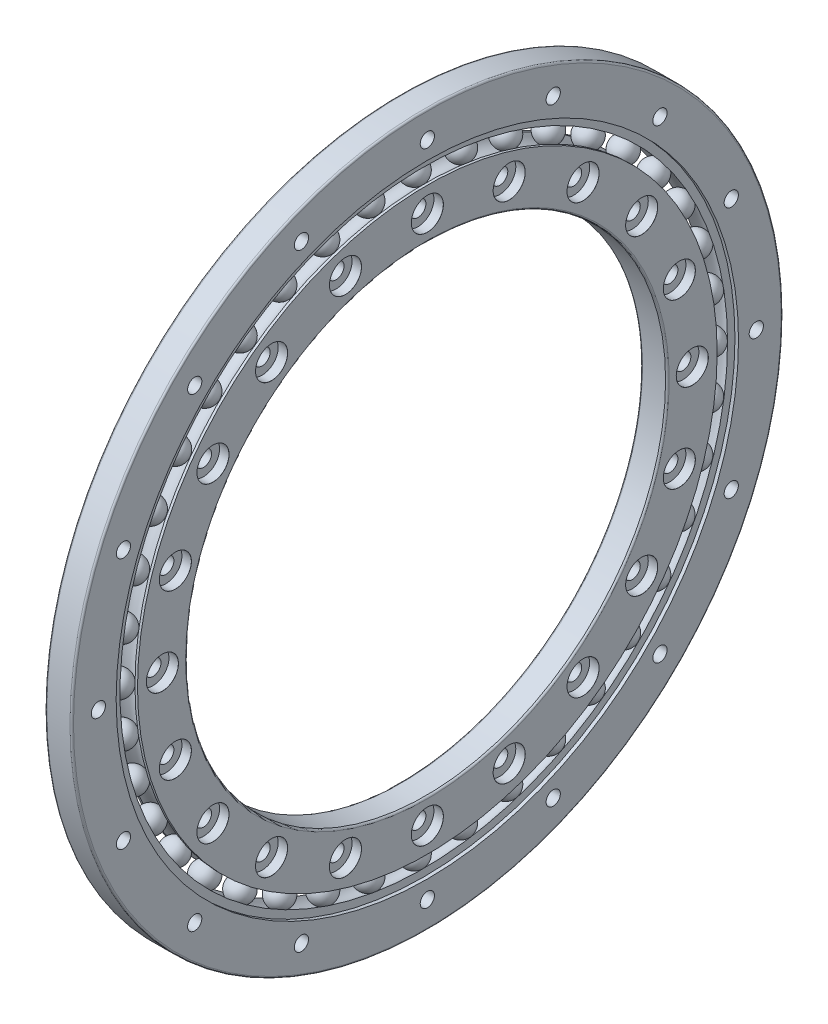
SolidWorks part; units mm, degrees
ref_plane "Front Plane" through (0, 0, 0) normal (0, 0, 1) x (1, 0, 0)
ref_plane "Top Plane" through (0, 0, 0) normal (0, 1, 0) x (1, 0, 0)
ref_plane "Right Plane" through (0, 0, 0) normal (1, 0, 0) x (0, 0, -1)
sketch "Sketch1" plane through (0, 0, 0) normal (0, 0, 1) x (1, 0, 0)
  line L0 (0, 0) -> (0, 185) construction
  line L1 (-4.3728, 170) -> (-4.3728, 163) construction
  line L2 (7.5, 170) -> (-7.5, 170)
  line L3 (7.5, 170) -> (7.5, 200)
  line L4 (7.5, 200) -> (-7.5, 200)
  line L5 (-7.5, 170) -> (-7.5, 200)
  line L6 (7.5, 170) -> (-7.5, 200) construction
  line L7 (7.5, 200) -> (-7.5, 170) construction
  line L8 (7.5, 163) -> (-7.5, 163)
  line L9 (7.5, 163) -> (7.5, 135)
  line L10 (7.5, 135) -> (-7.5, 135)
  line L11 (-7.5, 163) -> (-7.5, 135)
  line L12 (7.5, 163) -> (-7.5, 135) construction
  line L13 (7.5, 135) -> (-7.5, 163) construction
  line L14 (-4.3728, 166.5) -> (0, 166.5) construction
  line L15 (0, 0) -> (-68.3739, 0) construction
  circle A0 centre (0, 166.5) radius 7
  point P7 (0, 149)
  dimension "D6" = 14
  dimension "D1" = 15
  dimension "D2" = 135
  dimension "D3" = 200
  dimension "D4" = 28
  dimension "D5" = 30
revolve "Revolve1" add sketch "Sketch1" angle 360 about L15 region at (0, 185.9722, 0) region at (0, 148.0302, 0)
sketch "Sketch4" plane through (-7.5, 0, 0) normal (-1, 0, 0) x (0, 0, 1)
  circle A1 centre (0, 0) radius 170 construction
  circle A2 centre (0, 0) radius 170
  circle A3 centre (0, 0) radius 175
  dimension "D1" = 5
extrude "Cut-Extrude1" cut sketch "Sketch4" against normal blind 2
mirror "Mirror1" about plane through (0, 0, 0) normal (1, 0, 0) of "Cut-Extrude1"
fillet "Fillet1" radius 1 2 edges at (7.5, 0, -200) (-7.5, 0, -200)
fillet "Fillet2" radius 1 2 edges at (7.5, 0, -135) (-7.5, 0, -135)
sketch "Sketch6" plane through (0, 0, 0) normal (0, 1, 0) x (1, 0, 0)
  line L0 (-6.9, 166.5) -> (6.9, 166.5)
  arc A0 (6.9, 166.5) -> (-6.9, 166.5) centre (0, 166.5) ccw
  dimension "D2" = 13.8
  dimension "D1" = 166.5
revolve "Revolve2" add sketch "Sketch6" angle 360 about L0
ref_axis "Axis1" through (-89.8942, 0, 0) along (1, 0, 0)
pattern_circular "CirPattern1" count 40 over 360 about axis through (-89.8942, 0, 0) along (1, 0, 0) of bodies 105
sketch "Sketch7" plane through (7.5, 0, 0) normal (1, 0, 0) x (0, 0, -1)
  line L0 (0, 163) -> (0, 135) construction
  circle A0 centre (0, 0) radius 135 construction
  circle A1 centre (0, 0) radius 163 construction
  circle A2 centre (0, 0) radius 135 construction
  circle A3 centre (0, 0) radius 163 construction
  point P8 (0, 149)
  point P9 (0, 0)
hole_wizard "CBORE for M8 Hex Head Bolt1" positions "3DSketch3" profile "Sketch8" counterbore size "M8" standard "ISO" end condition through all
sketch3d "3DSketch3"
  point P0 (7.5, 149, 0)
sketch "Sketch8" plane through (7.5, 149, 0) normal (0, 1, 0) x (0, 0, -1)
  line L0 (0, 0) -> (0, 15)
  line L1 (0, 15) -> (4.5, 15)
  line L3 (4.5, 15) -> (4.5, 5.3)
  line L4 (9.0055, 5.3) -> (4.5, 5.3)
  line L5 (9.0055, 5.3) -> (9.0055, 0.025)
  line L6 (9.0055, 0.025) -> (9.0305, 0)
  line L7 (9.0305, 0) -> (0, 0)
  line L8 (-9.0055, 0.025) -> (-9.0305, 0) construction
  line L11 (0, -6.35) -> (0, 107.95) construction
  dimension "Thru Hole Dia." = 9
  dimension "Thru Hole Depth" = 15
  dimension "C'Bore Dia." = 18.011
  dimension "C'Bore Depth" = 5.3
  dimension "Near C'Sink Dia." = 18.061
  dimension "Near C'Sink Angle" = 90
pattern_circular "CirPattern2" count 20 over 360 about axis through (-89.8942, 0, 0) along (1, 0, 0) of "CBORE for M8 Hex Head Bolt1"
sketch "Sketch9" plane through (7.5, 0, 0) normal (1, 0, 0) x (0, 0, -1)
  point P0 (0, 0)
  point P7 (0, 185)
  dimension "D1" = 185
hole_wizard "Ø8.0mm Dowel Hole1" positions "3DSketch7" profile "Sketch12" hole size "Ø8.0" standard "ISO" end condition through all
sketch3d "3DSketch7"
  point P0 (7.5, 185, 0)
sketch "Sketch12" plane through (7.5, 185, 0) normal (0, 1, 0) x (0, 0, -1)
  line L0 (0, 0) -> (0, 15)
  line L1 (0, 15) -> (4, 15)
  line L2 (4, 15) -> (4, 0)
  line L5 (4, 0) -> (0, 0)
  line L11 (0, -6.35) -> (0, 107.95) construction
  dimension "Thru Hole Dia." = 8
  dimension "Thru Hole Depth" = 15
pattern_circular "CirPattern3" count 16 over 360 about axis through (-89.8942, 0, 0) along (1, 0, 0) of "Ø8.0mm Dowel Hole1"
